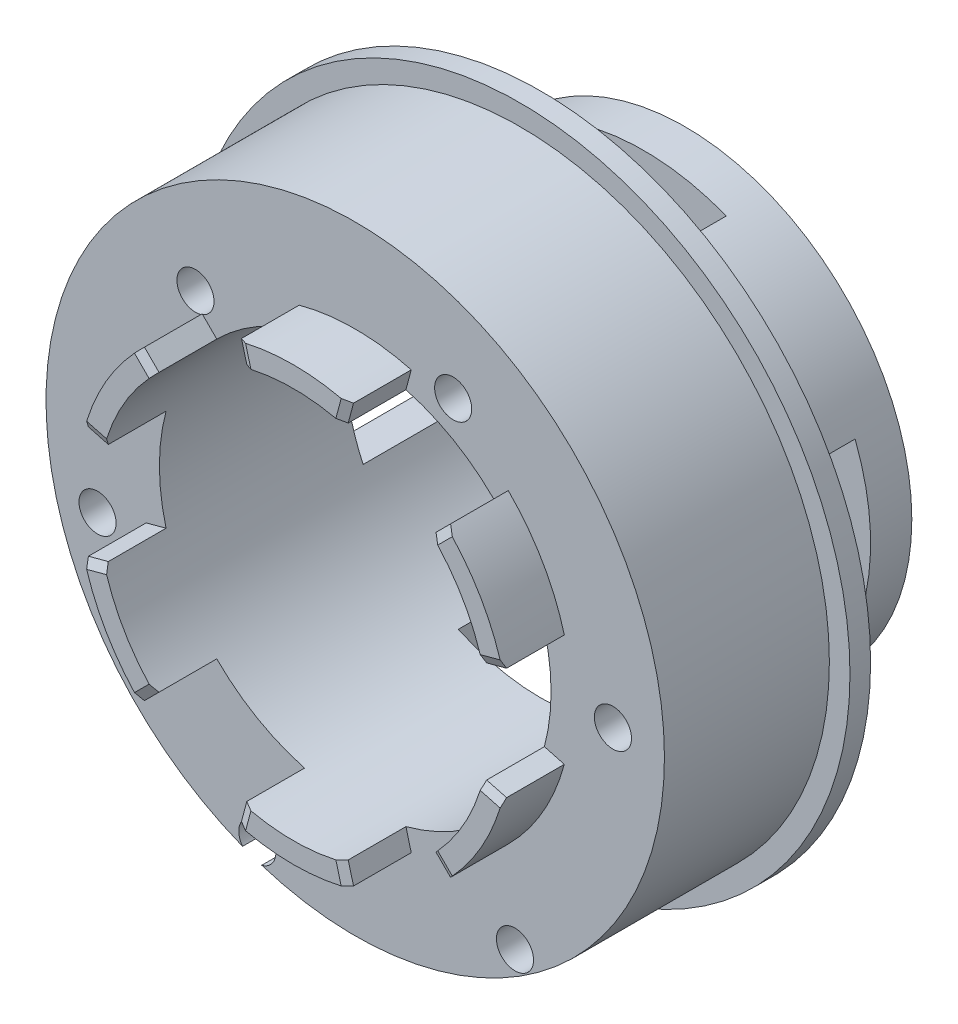
SolidWorks part; units mm, degrees
ref_plane "정면" through (0, 0, 0) normal (0, 0, 1) x (1, 0, 0)
ref_plane "윗면" through (0, 0, 0) normal (0, 1, 0) x (1, 0, 0)
ref_plane "우측면" through (0, 0, 0) normal (1, 0, 0) x (0, 0, -1)
sketch "스케치1" plane through (0, 0, 0) normal (0, 0, 1) x (1, 0, 0)
  circle A0 centre (0, 0) radius 11
  dimension "D1" = 22
extrude "보스-돌출1" add sketch "스케치1" along normal blind 2
sketch "스케치2" plane through (0, 0, 2) normal (0, 0, 1) x (1, 0, 0)
  circle A0 centre (0, 0) radius 11
  circle A1 centre (0, 0) radius 9.5
  circle A5 centre (0, 0) radius 11 construction
  dimension "D1" = 1.5
extrude "보스-돌출2" add sketch "스케치2" along normal blind 5
sketch "스케치4" plane through (0, 0, 7) normal (0, 0, 1) x (1, 0, 0)
  circle A0 centre (0, 0) radius 16
  circle A1 centre (0, 0) radius 9.5
  circle A2 centre (0, 0) radius 9.5 construction
  dimension "D1" = 32
extrude "보스-돌출3" add sketch "스케치4" along normal blind 1
sketch "스케치5" plane through (0, 0, 8) normal (0, 0, 1) x (1, 0, 0)
  circle A0 centre (0, 0) radius 9.5
  circle A1 centre (0, 0) radius 15
  circle A2 centre (0, 0) radius 9.5 construction
  dimension "D1" = 30
extrude "보스-돌출4" add sketch "스케치5" along normal blind 8
sketch "스케치6" plane through (0, 0, 16) normal (0, 0, 1) x (1, 0, 0)
  circle A0 centre (0, 0) radius 12.5 construction
  circle A6 centre (0, 0) radius 9.5 construction
  circle A8 centre (12.5, 0) radius 0.9
  circle A9 centre (7.75, -11.6913) radius 0.9
  circle A10 centre (-4.75, -13.4234) radius 0.9
  circle A11 centre (-12.5, -3.4641) radius 0.9
  circle A12 centre (-7.75, 8.2272) radius 0.9
  circle A13 centre (4.75, 9.9593) radius 0.9
  point P19 (0, -1.7321)
  point P20 (0, 0)
  dimension "D1" = 3
  dimension "D2" = 1.8
  dimension "D3" = 6
extrude "컷-돌출1" cut sketch "스케치6" against normal blind 8
sketch "스케치7" plane through (0, 0, 0) normal (0, 0, -1) x (-1, 0, 0)
  circle A0 centre (0, 0) radius 8 construction
  circle A5 centre (0, 0) radius 3
  circle A6 centre (-8, 0) radius 1
  circle A7 centre (8, 0) radius 1
  circle A9 centre (0, 8) radius 1
  circle A11 centre (0, -8) radius 1
  dimension "D1" = 16
  dimension "D2" = 2
  dimension "D4" = 6
extrude "컷-돌출2" cut sketch "스케치7" against normal through all
sketch "스케치8" plane through (0, 0, 0) normal (0, 1, 0) x (1, 0, 0)
  line L0 (11, 0) -> (-11, 0) construction
  line L1 (-4, -2) -> (4, -2)
  line L2 (-4, -2) -> (-4, -7)
  line L3 (-4, -7) -> (4, -7)
  line L4 (4, -2) -> (4, -7)
  line L5 (-4, -2) -> (4, -7) construction
  line L6 (-4, -7) -> (4, -2) construction
  line L8 (11, -7) -> (11, 0) construction
  line L9 (-11, 0) -> (-11, -7) construction
  line L10 (11, -7) -> (-11, -7) construction
  point P0 (0, -4.5)
  dimension "D1" = 2
  dimension "D3" = 7
  dimension "D4" = 7
extrude "컷-돌출3" cut sketch "스케치8" against normal through all both and the other way through all
sketch "스케치9" plane through (0, 0, 0) normal (1, 0, 0) x (0, 0, -1)
  line L0 (-7, -10.247) -> (-7, 10.247) construction
  line L1 (-7, -4) -> (-2, -4)
  line L2 (-7, -4) -> (-7, 4)
  line L3 (-7, 4) -> (-2, 4)
  line L4 (-2, -4) -> (-2, 4)
  line L5 (0, 11) -> (-2, 11) construction
  line L6 (-2, -11) -> (0, -11) construction
  line L7 (0, -11) -> (0, 11) construction
  dimension "D1" = 7
  dimension "D2" = 7
  dimension "D3" = 2
extrude "컷-돌출4" cut sketch "스케치9" against normal through all both and the other way through all
sketch "스케치10" plane through (0, 0, 16) normal (0, 0, 1) x (1, 0, 0)
  line L1 (2.4588, 9.1763) -> (2.7176, 10.1422)
  line L3 (6.7175, 6.7175) -> (7.4246, 7.4246)
  line L5 (9.1763, 2.4588) -> (10.1422, 2.7176)
  line L7 (9.1763, -2.4588) -> (10.1422, -2.7176)
  line L9 (6.7175, -6.7175) -> (7.4246, -7.4246)
  line L11 (2.4588, -9.1763) -> (2.7176, -10.1422)
  line L13 (-2.4588, -9.1763) -> (-2.7176, -10.1422)
  line L15 (-6.7175, -6.7175) -> (-7.4246, -7.4246)
  line L17 (-9.1763, -2.4588) -> (-10.1422, -2.7176)
  line L19 (-9.1763, 2.4588) -> (-10.1422, 2.7176)
  line L21 (-6.7175, 6.7175) -> (-7.4246, 7.4246)
  line L23 (-2.4588, 9.1763) -> (-2.7176, 10.1422)
  arc A0 (-7.4246, 7.4246) -> (-10.1422, 2.7176) centre (0, 0) ccw
  arc A1 (-9.1763, -2.4588) -> (-6.7175, -6.7175) centre (0, 0) ccw
  arc A2 (2.7176, 10.1422) -> (-2.7176, 10.1422) centre (0, 0) ccw
  arc A3 (10.1422, 2.7176) -> (7.4246, 7.4246) centre (0, 0) ccw
  arc A4 (7.4246, -7.4246) -> (10.1422, -2.7176) centre (0, 0) ccw
  arc A5 (-2.7176, -10.1422) -> (2.7176, -10.1422) centre (0, 0) ccw
  arc A6 (-10.1422, -2.7176) -> (-7.4246, -7.4246) centre (0, 0) ccw
  arc A7 (-2.4588, -9.1763) -> (2.4588, -9.1763) centre (0, 0) ccw
  arc A8 (6.7175, -6.7175) -> (9.1763, -2.4588) centre (0, 0) ccw
  arc A9 (9.1763, 2.4588) -> (6.7175, 6.7175) centre (0, 0) ccw
  arc A10 (2.4588, 9.1763) -> (-2.4588, 9.1763) centre (0, 0) ccw
  arc A11 (-6.7175, 6.7175) -> (-9.1763, 2.4588) centre (0, 0) ccw
  point P30 (0, 0)
  dimension "D1" = 1
extrude "보스-돌출5" add sketch "스케치10" along normal blind 3
chamfer "모따기1" distance 0.2 angle 64 12 edges at (-9.6593, -2.5882, 19) (-7.0711, -7.0711, 19) (-2.5882, -9.6593, 19) (2.5882, -9.6593, 19) (7.0711, -7.0711, 19) (9.6593, -2.5882, 19) (9.6593, 2.5882, 19) (7.0711, 7.0711, 19) (2.5882, 9.6593, 19) (-2.5882, 9.6593, 19) (-7.0711, 7.0711, 19) (-9.6593, 2.5882, 19) first distance on face at (-9.6593, -2.5882, 17.5) first distance on face at (-7.0711, -7.0711, 17.5) first distance on face at (-2.5882, -9.6593, 17.5) first distance on face at (2.5882, -9.6593, 17.5) first distance on face at (7.0711, -7.0711, 17.5) first distance on face at (9.6593, -2.5882, 17.5) first distance on face at (9.6593, 2.5882, 17.5) first distance on face at (7.0711, 7.0711, 17.5) first distance on face at (2.5882, 9.6593, 17.5) first distance on face at (-2.5882, 9.6593, 17.5) first distance on face at (-7.1366, 7.1366, 17.2) first distance on face at (-9.6593, 2.5882, 17.5)
